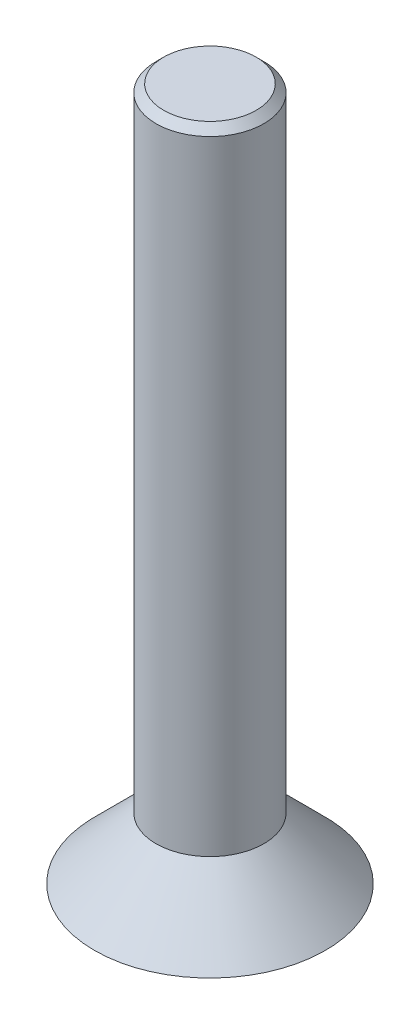
SolidWorks part; units mm, degrees
material "铸造合金钢"
ref_plane "前视基准面" through (0, 0, 0) normal (0, 0, 1) x (1, 0, 0)
ref_plane "上视基准面" through (0, 0, 0) normal (0, 1, 0) x (1, 0, 0)
ref_plane "右视基准面" through (0, 0, 0) normal (1, 0, 0) x (0, 0, -1)
sketch "草图1" plane through (0, 0, 0) normal (0, 1, 0) x (1, 0, 0)
  line L1 (0, -1.1547) -> (1, -0.5774)
  line L2 (1, -0.5774) -> (1, 0.5774)
  line L3 (1, 0.5774) -> (0, 1.1547)
  line L4 (0, 1.1547) -> (-1, 0.5774)
  line L5 (-1, 0.5774) -> (-1, -0.5774)
  line L6 (-1, -0.5774) -> (0, -1.1547)
  circle A0 centre (0, 0) radius 3
  circle A1 centre (0, 0) radius 1 construction
  dimension "D1" = 6
  dimension "D2" = 2
extrude "凸台-拉伸1" add sketch "草图1" along normal blind 1.6
chamfer "倒角1" distance 1.6 angle 45 1 edges at (0, 1.6, 3)
sketch "草图2" plane through (0, 1.6, 0) normal (0, 1, 0) x (1, 0, 0)
  circle A0 centre (0, 0) radius 1.4
  dimension "D1" = 2.8
extrude "凸台-拉伸2" add sketch "草图2" along normal blind 16.4
chamfer "倒角2" distance 0.2 angle 45 1 edges at (0, 18, 1.4)
